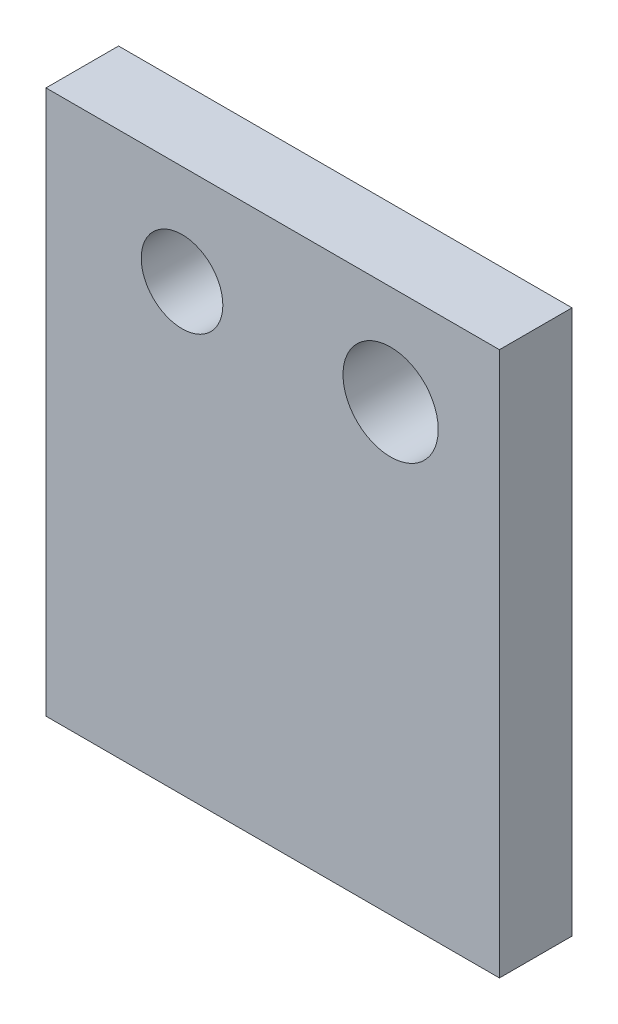
SolidWorks part; units mm, degrees
ref_plane "Front Plane" through (0, 0, 0) normal (0, 0, 1) x (1, 0, 0)
ref_plane "Top Plane" through (0, 0, 0) normal (0, 1, 0) x (1, 0, 0)
ref_plane "Right Plane" through (0, 0, 0) normal (1, 0, 0) x (0, 0, -1)
sketch "Sketch1" plane through (0, 0, 0) normal (0, 0, 1) x (1, 0, 0)
  line L1 (-25, -30) -> (25, -30)
  line L2 (-25, -30) -> (-25, 30)
  line L3 (-25, 30) -> (25, 30)
  line L4 (25, -30) -> (25, 30)
  line L5 (-25, -30) -> (25, 30) construction
  line L6 (-25, 30) -> (25, -30) construction
  circle A0 centre (-10, 19) radius 4.5
  point P0 (0, 0)
  dimension "D3" = 11
  dimension "D5" = 9
  dimension "D1" = 60
  dimension "D2" = 50
  dimension "D4" = 15
extrude "Boss-Extrude1" add sketch "Sketch1" along normal blind 8
sketch "Sketch2" plane through (0, 0, 0) normal (0, 0, 1) x (1, 0, 0)
  line L0 (25, 30) -> (-25, 30) construction
  line L1 (-25, 30) -> (-25, -30) construction
  circle A0 centre (13, 19) radius 5.25
  dimension "D1" = 10.5
  dimension "D2" = 11
  dimension "D3" = 38
extrude "Cut-Extrude2" cut sketch "Sketch2" along normal through all
